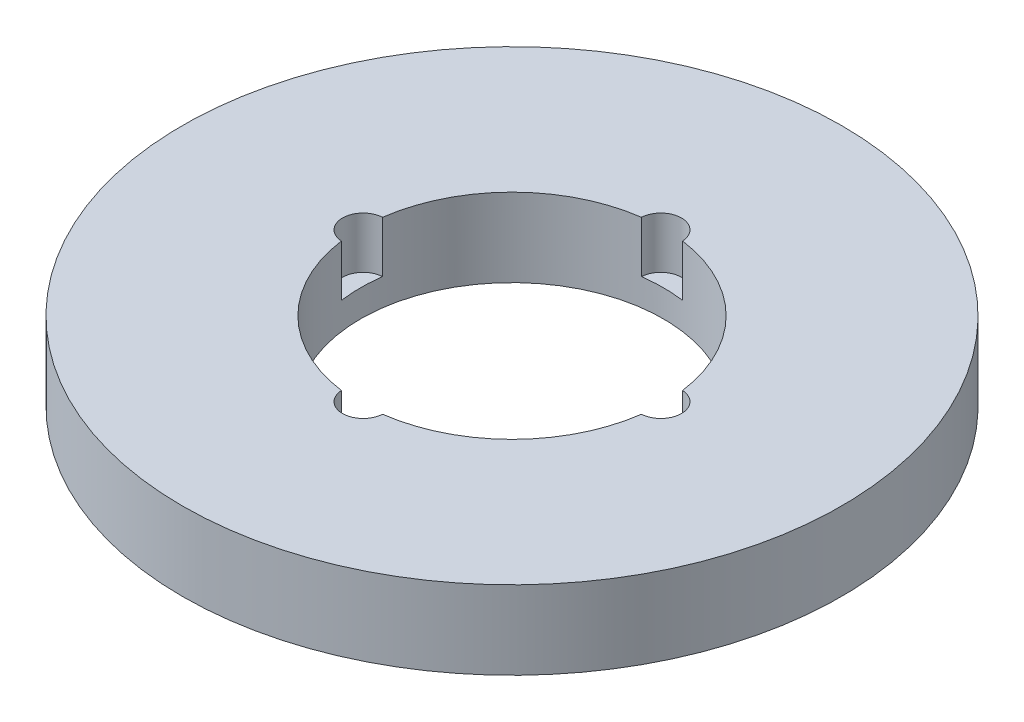
SolidWorks part; units mm, degrees
ref_plane "Front Plane" through (0, 0, 0) normal (0, 0, 1) x (1, 0, 0)
ref_plane "Top Plane" through (0, 0, 0) normal (0, 1, 0) x (1, 0, 0)
ref_plane "Right Plane" through (0, 0, 0) normal (1, 0, 0) x (0, 0, -1)
sketch "Sketch1" plane through (0, 0, 0) normal (0, 1, 0) x (1, 0, 0)
  circle A0 centre (0, 0) radius 92.5
  dimension "FLANGE_OD" = 185
extrude "Boss-Extrude1" add sketch "Sketch1" along normal blind 22
sketch "Sketch2" plane through (0, 0, 0) normal (0, 1, 0) x (1, 0, 0)
  circle A0 centre (0, 0) radius 42.5
  dimension "BORE_D" = 85
extrude "Cut-Extrude1" cut sketch "Sketch2" along normal through all
sketch "Sketch3" plane through (0, 22, 0) normal (0, 1, 0) x (1, 0, 0)
  circle A0 centre (0, 0) radius 41.7692 construction
  circle A1 centre (-41.7692, 0) radius 5.7874
  dimension "BOLT_D" = 11.5749
  dimension "BOLT_PCD" = 83.5384
extrude "Cut-Extrude2" cut sketch "Sketch3" against normal blind 14.4239
pattern_circular "CirPattern1" count 4 over 360 about axis through (0, 0, 0) along (0, 1, 0) of "Cut-Extrude2"
